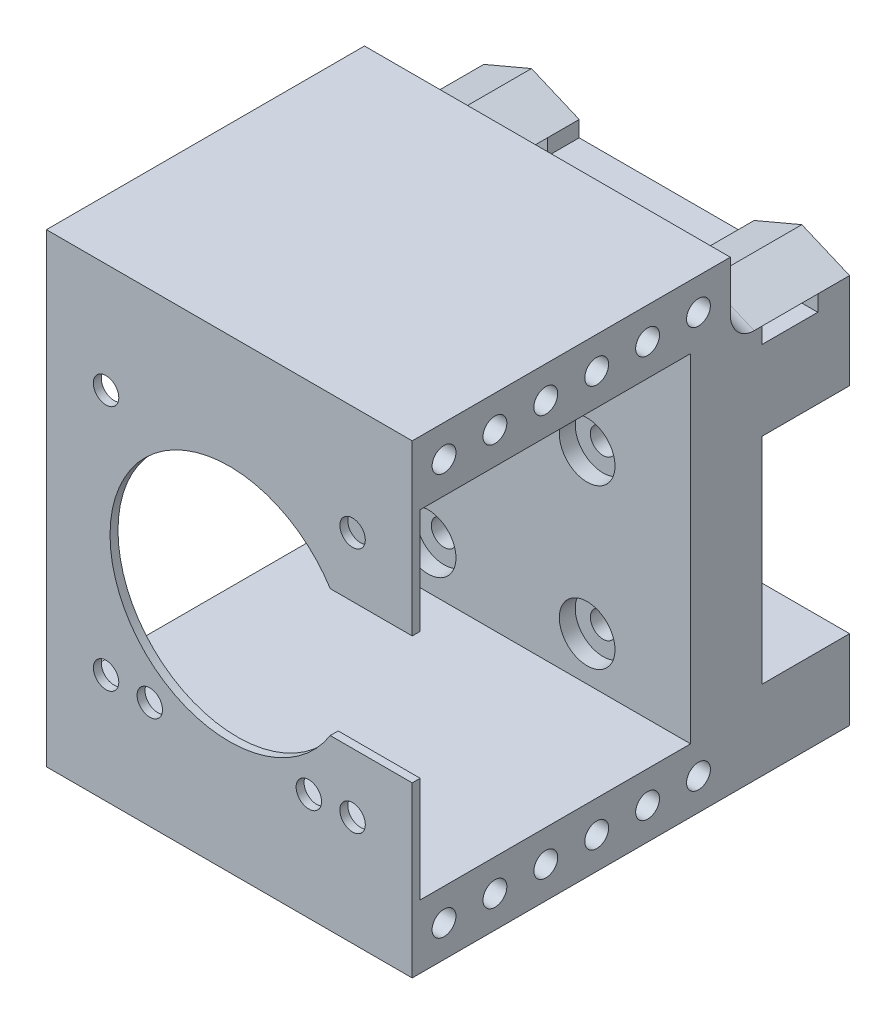
SolidWorks part; units mm, degrees
ref_plane "Front Plane" through (0, 0, 0) normal (0, 0, 1) x (1, 0, 0)
ref_plane "Top Plane" through (0, 0, 0) normal (0, 1, 0) x (1, 0, 0)
ref_plane "Right Plane" through (0, 0, 0) normal (1, 0, 0) x (0, 0, -1)
sketch "Sketch1" plane through (0, 0, 0) normal (0, 0, 1) x (1, 0, 0)
  line L5 (-23, -23.5) -> (23, -23.5)
  line L6 (-23, -23.5) -> (-23, 23.5)
  line L7 (-23, 23.5) -> (23, 23.5)
  line L8 (23, -23.5) -> (23, 23.5)
  line L9 (-23, -23.5) -> (23, 23.5) construction
  line L10 (-23, 23.5) -> (23, -23.5) construction
  point P0 (0, 0)
  dimension "D1" = 46
  dimension "D2" = 47
extrude "Boss-Extrude1" add sketch "Sketch1" along normal blind 9
sketch "Sketch3" plane through (0, 0, 0) normal (0, 0, 1) x (1, 0, 0)
  line L0 (23, -23.5) -> (23, 23.5) construction
  line L1 (23, 23.5) -> (-23, 23.5)
  line L2 (23, 23.5) -> (23, 13.5)
  line L3 (23, 13.5) -> (-23, 13.5)
  line L4 (-23, 23.5) -> (-23, 13.5)
  line L5 (-23, 23.5) -> (-23, -23.5) construction
  line L7 (23, -23.5) -> (-23, -23.5)
  line L8 (23, -23.5) -> (23, -13.5)
  line L9 (23, -13.5) -> (-23, -13.5)
  line L10 (-23, -23.5) -> (-23, -13.5)
  dimension "D1" = 13.5
  dimension "D2" = 10
  dimension "D3" = 10
extrude "Boss-Extrude2" add sketch "Sketch3" against normal blind 11
sketch "Sketch4" plane through (0, 0, 0) normal (0, 0, 1) x (1, 0, 0)
  line L0 (23, 23.5) -> (-23, 23.5) construction
  line L1 (-23, 23.5) -> (-23, -23.5) construction
  circle A0 centre (-17, 18.5) radius 2.15
  circle A1 centre (17, 18.5) radius 2.15
  circle A2 centre (-17, -18.5) radius 2.15
  circle A3 centre (17, -18.5) radius 2.15
  dimension "D1" = 4.3
  dimension "D5" = 2
  dimension "D2" = 5
  dimension "D3" = 6
  dimension "D6" = 34
  dimension "D7" = 37
  dimension "D4" = 2
extrude "Cut-Extrude2" [suppressed] cut sketch "Sketch4" against normal through all both and the other way through all
sketch "Sketch7" plane through (0, 0, -11) normal (0, 0, -1) x (-1, 0, 0)
  line L0 (0, 23.5) -> (0, 39.2593) construction
  line L4 (-23, 23.5) -> (23, 23.5) construction
  line L5 (-23, 23.5) -> (-11, 23.5)
  line L6 (-23, 23.5) -> (-23, 25.5)
  line L8 (-11, 23.5) -> (-11, 25.5)
  line L9 (-23, 25.5) -> (-17, 28.0449)
  line L14 (-17, 28.0449) -> (-11, 25.5)
  line L15 (17, 28.0449) -> (11, 25.5)
  line L16 (23, 25.5) -> (17, 28.0449)
  line L17 (11, 23.5) -> (11, 25.5)
  line L18 (23, 23.5) -> (23, 25.5)
  line L19 (23, 23.5) -> (11, 23.5)
  line L20 (-17, 23.5) -> (-17, 30.4296) construction
  dimension "D1" = 2
  dimension "D2" = 2
extrude "Boss-Extrude5" add sketch "Sketch7" against normal blind 15
sketch "Sketch8" plane through (0, 0, 0) normal (1, 0, 0) x (0, 0, -1)
  line L0 (-4, 23.5) -> (11, 23.5) construction
  line L1 (7, 23.5) -> (0, 23.5)
  line L2 (7, 23.5) -> (7, 25.5)
  line L3 (7, 25.5) -> (0, 25.5)
  line L4 (0, 23.5) -> (0, 25.5)
  line L6 (11, 23.5) -> (11, 25.5) construction
  dimension "D1" = 4
  dimension "D2" = 7
extrude "Cut-Extrude3" cut sketch "Sketch8" against normal through all both and the other way through all
sketch "Sketch10" [suppressed] plane through (0, 0, -11) normal (0, 0, -1) x (-1, 0, 0)
  circle A0 centre (-17, -18.5) radius 3.2
  circle A1 centre (17, -18.5) radius 3.2
  circle A2 centre (17, 18.5) radius 3.2
  circle A3 centre (-17, 18.5) radius 3.2
  dimension "D1" = 6.4
extrude "Cut-Extrude5" [suppressed] cut sketch "Sketch10" against normal blind 13
ref_plane "Plane1" through (0, 0, 9) normal (0, 0, 1) x (1, 0, 0)
sketch "Sketch11" plane through (0, 0, 9) normal (0, 0, 1) x (1, 0, 0)
  line L0 (23, -23.5) -> (23, 23.5) construction
  line L1 (-23, -23.5) -> (23, -23.5)
  line L2 (-23, -23.5) -> (-23, -15.5)
  line L3 (-23, -15.5) -> (23, -15.5)
  line L4 (23, -23.5) -> (23, -15.5)
  line L5 (-23, 23.5) -> (-23, -23.5) construction
  line L6 (-23, 27) -> (23, 27)
  line L7 (-23, 27) -> (-23, 35)
  line L8 (-23, 35) -> (23, 35)
  line L9 (23, 27) -> (23, 35)
  dimension "D1" = 8
  dimension "D2" = 8
  dimension "D3" = 42.5
extrude "Boss-Extrude6" add sketch "Sketch11" along normal blind 34
ref_plane "Plane2" through (0, 0, 43) normal (0, 0, 1) x (1, 0, 0)
sketch "Sketch12" plane through (0, 0, 43) normal (0, 0, 1) x (1, 0, 0)
  line L1 (-23, 35) -> (23, 35)
  line L2 (-23, 35) -> (-23, -23.5)
  line L3 (-23, -23.5) -> (23, -23.5)
  line L4 (23, 35) -> (23, -23.5)
extrude "Boss-Extrude7" add sketch "Sketch12" along normal blind 1
sketch "Sketch13" plane through (0, 0, 44) normal (0, 0, 1) x (1, 0, 0)
  line L0 (-23, -23.5) -> (23, -23.5) construction
  line L1 (23, -23.5) -> (23, 35) construction
  line L2 (-15.5, -9.75) -> (15.5, -9.75) construction
  line L3 (-15.5, -9.75) -> (-15.5, 21.25) construction
  line L4 (-15.5, 21.25) -> (15.5, 21.25) construction
  line L5 (15.5, -9.75) -> (15.5, 21.25) construction
  line L6 (-15.5, -9.75) -> (15.5, 21.25) construction
  line L7 (-15.5, 21.25) -> (15.5, -9.75) construction
  circle A0 centre (0, 5.75) radius 15
  circle A1 centre (-15.5, 21.25) radius 1.6
  circle A2 centre (15.5, 21.25) radius 1.6
  circle A3 centre (15.5, -9.75) radius 1.6
  circle A4 centre (-15.5, -9.75) radius 1.6
  dimension "D1" = 30
  dimension "D6" = 3.2
  dimension "D2" = 29.25
  dimension "D3" = 23
  dimension "D4" = 31
  dimension "D5" = 31
extrude "Cut-Extrude6" cut sketch "Sketch13" against normal up to next
sketch "Sketch14" plane through (0, 23.5, 0) normal (0, 1, 0) x (1, 0, 0)
  line L1 (23, -4) -> (-23, -4)
  line L2 (23, -4) -> (23, -9)
  line L3 (23, -9) -> (-23, -9)
  line L4 (-23, -4) -> (-23, -9)
extrude "Boss-Extrude8" add sketch "Sketch14" along normal up to surface (11.5 mm away) up to face at (0, 35, 26.5)
sketch "Sketch15" plane through (0, 0, 44) normal (0, 0, 1) x (1, 0, 0)
  line L0 (23, -23.5) -> (23, 35) construction
  line L1 (7, -2.248) -> (23, -2.248)
  line L2 (7, -2.248) -> (7, 13.748)
  line L3 (7, 13.748) -> (23, 13.748)
  line L4 (23, -2.248) -> (23, 13.748)
  line L5 (7, -2.248) -> (23, 13.748) construction
  line L6 (7, 13.748) -> (23, -2.248) construction
  circle A0 centre (0, 5.75) radius 15 construction
  point P0 (15, 5.75)
extrude "Cut-Extrude7" cut sketch "Sketch15" against normal blind 3
sketch "Sketch2" plane through (0, 0, 9) normal (0, 0, 1) x (1, 0, 0)
  circle A0 centre (-10, 10) radius 1.6
  circle A3 centre (10, 10) radius 1.6
  circle A4 centre (-10, -10) radius 1.6
  circle A5 centre (10, -10) radius 1.6
  dimension "D1" = 3.2
  dimension "D2" = 10
  dimension "D3" = 10
  dimension "D4" = 2
  dimension "D5" = 2
extrude "Cut-Extrude1" cut sketch "Sketch2" against normal through all both and the other way through all
sketch "Sketch9" plane through (0, 0, 9) normal (0, 0, 1) x (1, 0, 0)
  circle A0 centre (-10, 10) radius 3.5
  circle A1 centre (10, 10) radius 3.5
  circle A2 centre (10, -10) radius 3.5
  circle A3 centre (-10, -10) radius 3.5
  dimension "D1" = 7
extrude "Cut-Extrude4" cut sketch "Sketch9" against normal blind 2
fillet "Fillet1" radius 3 7 edges at (-20, 26.7724, 4) (-14, 26.7724, 4) (-11, 24.5, 4) (11, 24.5, 4) (0, 23.5, 4) (20, 26.7724, 4) (14, 26.7724, 4)
sketch "Sketch17" plane through (-23, 0, 0) normal (-1, 0, 0) x (0, 0, 1)
  line L0 (4, 35) -> (4, 28.7587) construction
  line L1 (44, 35) -> (44, -23.5) construction
  line L2 (44, -23.5) -> (-11, -23.5) construction
  line L4 (44, 35) -> (4, 35) construction
  circle A11 centre (40, -19.5) radius 1.5
  circle A12 centre (33.6, -19.5) radius 1.5
  circle A13 centre (27.2, -19.5) radius 1.5
  circle A14 centre (20.8, -19.5) radius 1.5
  circle A15 centre (14.4, -19.5) radius 1.5
  circle A16 centre (8, -19.5) radius 1.5
  circle A20 centre (33.6, 31) radius 1.5
  circle A21 centre (27.2, 31) radius 1.5
  circle A22 centre (20.8, 31) radius 1.5
  circle A23 centre (14.4, 31) radius 1.5
  circle A24 centre (8, 31) radius 1.5
  circle A28 centre (40, 31) radius 1.5
  dimension "D3" = 3
  dimension "D6" = 4
  dimension "D1" = 4
  dimension "D2" = 4
  dimension "D7" = 4
  dimension "D4" = 6
  dimension "D5" = 2
extrude "Cut-Extrude8" cut sketch "Sketch17" against normal through all
sketch "Sketch18" plane through (0, -23.5, 0) normal (0, -1, 0) x (1, 0, 0)
  circle A0 centre (17.9986, 5.7624) radius 1.5
  circle A1 centre (0.0004, 5.7641) radius 1.5
  dimension "D1" = 3
  dimension "D2" = 3
extrude "Cut-Extrude9" cut sketch "Sketch18" against normal blind 8
sketch "Sketch20" plane through (0, 0, -11) normal (0, 0, -1) x (-1, 0, 0)
  line L0 (-23, -23.5) -> (-23, -13.5) construction
  line L1 (23, -23.5) -> (-23, -23.5) construction
  line L2 (23, -13.5) -> (23, -23.5) construction
  line L3 (23, 13.5) -> (-23, 13.5) construction
  circle A0 centre (-19, -18.5) radius 1.5
  circle A1 centre (-12.6667, -18.5) radius 1.5
  circle A2 centre (-6.3333, -18.5) radius 1.5
  circle A3 centre (0, -18.5) radius 1.5
  circle A4 centre (6.3333, -18.5) radius 1.5
  circle A5 centre (12.6667, -18.5) radius 1.5
  circle A6 centre (19, -18.5) radius 1.5
  circle A7 centre (-19, 18.5) radius 1.5
  circle A8 centre (-12.6667, 18.5) radius 1.5
  circle A9 centre (-6.3333, 18.5) radius 1.5
  circle A10 centre (0, 18.5) radius 1.5
  circle A11 centre (6.3333, 18.5) radius 1.5
  circle A12 centre (12.6667, 18.5) radius 1.5
  circle A13 centre (19, 18.5) radius 1.5
  dimension "D1" = 3
  dimension "D2" = 4
  dimension "D3" = 5
  dimension "D5" = 4
  dimension "D7" = 5
  dimension "D4" = 7
  dimension "D6" = 2
extrude "Cut-Extrude10" cut sketch "Sketch20" against normal blind 10
